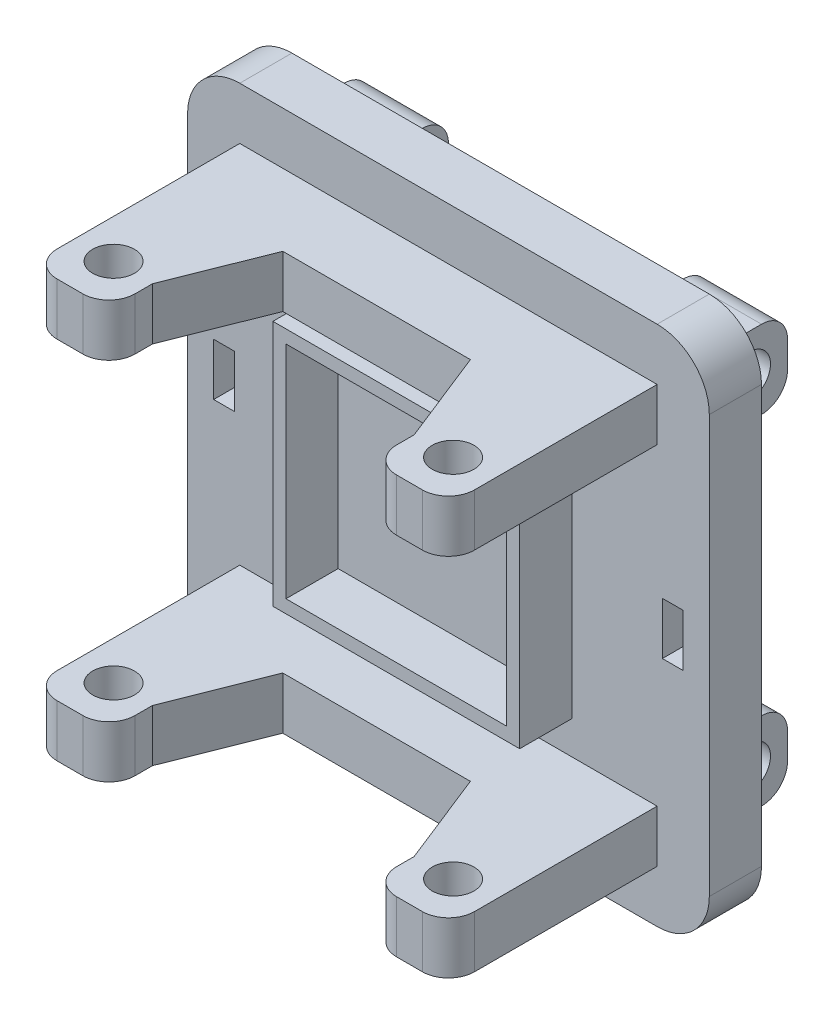
SolidWorks part; units mm, degrees
ref_plane "Piano frontale" through (0, 0, 0) normal (0, 0, 1) x (1, 0, 0)
ref_plane "Piano superiore" through (0, 0, 0) normal (0, 1, 0) x (1, 0, 0)
ref_plane "Piano destro" through (0, 0, 0) normal (1, 0, 0) x (0, 0, -1)
sketch "Schizzo1" plane through (0, 0, 0) normal (0, 0, 1) x (1, 0, 0)
  line L1 (-50, 50) -> (50, 50)
  line L2 (-50, 50) -> (-50, -50)
  line L3 (-50, -50) -> (50, -50)
  line L4 (50, 50) -> (50, -50)
  line L5 (-50, 50) -> (50, -50) construction
  line L6 (-50, -50) -> (50, 50) construction
  point P0 (0, 0)
  dimension "D1" = 100
  dimension "D2" = 100
extrude "Estrusione-Estrusione1" add sketch "Schizzo1" along normal blind 10
fillet "Raccordo1" radius 10 4 edges at (50, -50, 5) (-50, -50, 5) (50, 50, 5) (-50, 50, 5)
sketch "Schizzo5" plane through (0, 0, 0) normal (0, 0, -1) x (-1, 0, 0)
  line L0 (-50, 40) -> (50, 40) construction
  line L1 (50, 40) -> (-50, -40) construction
  line L2 (-50, -40) -> (-50, 40) construction
  line L3 (-50, -40) -> (50, -40) construction
  line L4 (50, -40) -> (-50, 40) construction
  line L5 (0, 57.1134) -> (0, 0) construction
  line L6 (0, 0) -> (66.1216, 0) construction
  arc A0 (-50, -40) -> (-40, -50) centre (-40, -40) ccw construction
ref_plane "Piano1" through (0, 0, 0) normal (0, 0, -1) x (-1, 0, 0)
sketch "Schizzo6" plane through (0, 0, 0) normal (0, 0, -1) x (-1, 0, 0)
  line L1 (-40, 40) -> (-25, 40)
  line L2 (-40, 40) -> (-40, 25)
  line L3 (-40, 25) -> (-25, 25)
  line L4 (-25, 40) -> (-25, 25)
  dimension "D1" = 15
  dimension "D2" = 15
extrude "Estrusione-Estrusione2" add sketch "Schizzo6" along normal blind 15
fillet "Raccordo2" radius 5 2 edges at (32.5, 25, -15) (32.5, 40, -15)
sketch "Schizzo7" plane through (40, 0, 0) normal (1, 0, 0) x (0, 0, -1)
  circle A0 centre (7.7265, 32.5421) radius 4
extrude "Taglio-Estrusione1" cut sketch "Schizzo7" against normal blind 15 contours A0
mirror "Specchia3" about plane through (0, 0, 0) normal (1, 0, 0) of "Estrusione-Estrusione2", "Taglio-Estrusione1"
fillet "Raccordo3" radius 5 2 edges at (-32.5, 25, -15) (-32.5, 40, -15)
mirror "Specchia6" about plane through (0, 0, 0) normal (0, 1, 0) of "Specchia3", "Raccordo3"
fillet "Raccordo4" radius 5 2 edges at (32.5, -40, -15) (32.5, -25, -15)
sketch "Schizzo8" plane through (0, 0, 10) normal (0, 0, 1) x (1, 0, 0)
  line L1 (-21.15, 21.15) -> (21.15, 21.15)
  line L2 (-21.15, 21.15) -> (-21.15, -21.15)
  line L3 (-21.15, -21.15) -> (21.15, -21.15)
  line L4 (21.15, 21.15) -> (21.15, -21.15)
  line L5 (-21.15, 21.15) -> (21.15, -21.15) construction
  line L6 (-21.15, -21.15) -> (21.15, 21.15) construction
  line L7 (-23.65, 23.65) -> (23.65, 23.65)
  line L8 (-23.65, 23.65) -> (-23.65, -23.65)
  line L9 (-23.65, -23.65) -> (23.65, -23.65)
  line L10 (23.65, 23.65) -> (23.65, -23.65)
  line L11 (-23.65, 23.65) -> (23.65, -23.65) construction
  line L12 (-23.65, -23.65) -> (23.65, 23.65) construction
  point P0 (0, 0)
  point P6 (0, 0)
  dimension "D1" = 42.3
  dimension "D2" = 42.3
  dimension "D3" = 47.3
  dimension "D4" = 47.3
extrude "Estrusione-Estrusione4" add sketch "Schizzo8" along normal blind 10
sketch "Schizzo10" plane through (0, 0, 10) normal (0, 0, 1) x (1, 0, 0)
  line L1 (40, -40) -> (-40, -40)
  line L2 (40, -40) -> (40, -30)
  line L3 (40, -30) -> (-40, -30)
  line L4 (-40, -40) -> (-40, -30)
  dimension "D1" = 10
extrude "Estrusione-Estrusione6" add sketch "Schizzo10" along normal blind 40 contours L2 L3 L4 L1
sketch "Schizzo11" plane through (0, -40, 0) normal (0, -1, 0) x (1, 0, 0)
  line L0 (-25.0784, 0) -> (-25.0784, 73.3) construction
  line L1 (50, 0) -> (-50, 0) construction
  line L2 (-25.0784, 73.3) -> (-40, 73.3) construction
  line L3 (-32.5392, 73.3) -> (-32.5392, 10) construction
  line L4 (-40, 10) -> (40, 10) construction
  line L5 (0, 0) -> (0, 59.9443) construction
  circle A0 centre (-32.5392, 41.65) radius 4
  circle A1 centre (32.5392, 41.65) radius 4
extrude "Taglio-Estrusione4" cut sketch "Schizzo11" against normal blind 30 contours A1
extrude "Taglio-Estrusione5" cut sketch "Schizzo11<4>" against normal blind 30
sketch "Schizzo11<4>" plane through (0, -40, 0) normal (0, -1, 0) x (1, 0, 0) same geometry as "Schizzo11"
fillet "Raccordo5" radius 5 1 edges at (-40, -35, 50)
fillet "Raccordo6" radius 5 1 edges at (40, -35, 50)
sketch "Schizzo14" plane through (0, -40, 0) normal (0, -1, 0) x (1, 0, 0)
  line L0 (-32.5392, 41.65) -> (-40, 41.65) construction
  line L1 (-40, 45) -> (-40, 10) construction
  line L2 (-32.5392, 41.65) -> (-25.0784, 41.65) construction
  line L3 (-25.0784, 41.65) -> (-25.0784, 50)
  line L4 (35, 50) -> (-35, 50) construction
  line L5 (-25.0784, 41.65) -> (-17.9796, 23.7762)
  line L6 (-17.9796, 23.7762) -> (17.9796, 23.7762)
  line L7 (0, 0) -> (0, 44.6599) construction
  line L8 (25.0784, 41.65) -> (25.0784, 50)
  line L9 (25.0784, 41.65) -> (17.9796, 23.7762)
  line L10 (-25.0784, 50) -> (25.0784, 50)
  point P17 (0, 23.7762)
  dimension "D1" = 7.4608
extrude "Taglio-Estrusione6" cut sketch "Schizzo14" against normal blind 30 contours L5 L6 L9 L8 L10 L3
fillet "Raccordo7" radius 5 1 edges at (-25.0784, -35, 50)
fillet "Raccordo8" radius 5 1 edges at (25.0784, -35, 50)
mirror "Specchia13" about plane through (0, 0, 0) normal (0, 1, 0) of "Estrusione-Estrusione6"
mirror "Specchia14" about plane through (0, 0, 0) normal (0, 1, 0) of "Estrusione-Estrusione6", "Taglio-Estrusione6"
fillet "Raccordo9" radius 5 4 edges at (-40, 35, 50) (-25.0784, 35, 50) (40, 35, 50) (25.0784, 35, 50)
sketch "Schizzo15" plane through (0, 40, 0) normal (0, 1, 0) x (1, 0, 0)
  line L0 (32.5392, -50) -> (32.5392, -33.3) construction
  line L1 (35, -50) -> (30.0784, -50) construction
  line L2 (0, 0) -> (0, -57.2659) construction
  circle A0 centre (32.5392, -41.65) radius 4
  circle A1 centre (-32.5392, -41.65) radius 4
  dimension "D1" = 8.35
extrude "Taglio-Estrusione7" cut sketch "Schizzo15" against normal blind 30 contours A0
extrude "Taglio-Estrusione8" cut sketch "Schizzo15<3>" against normal blind 30
sketch "Schizzo15<3>" plane through (0, 40, 0) normal (0, 1, 0) x (1, 0, 0) same geometry as "Schizzo15"
sketch "Schizzo16" plane through (0, 0, 0) normal (0, 0, -1) x (-1, 0, 0)
  line L0 (47.0711, 47.0711) -> (-47.0711, -47.0711) construction
  line L1 (0, 0) -> (43.631, 0) construction
  line L2 (47.0711, -47.0711) -> (-47.0711, 47.0711) construction
  line L4 (0, 47.0711) -> (0, -40) construction
  line L5 (-45, -5) -> (-41, -5)
  line L6 (-41, -5) -> (-41, 5)
  line L8 (-45, 5) -> (-41, 5)
  line L9 (-45, -5) -> (-45, 5)
  line L15 (0, 0) -> (-47.0711, 0) construction
  line L16 (50, 40) -> (50, -40) construction
  line L17 (45, -5) -> (41, -5)
  line L18 (45, -5) -> (45, 5)
  line L19 (45, 5) -> (41, 5)
  line L20 (41, -5) -> (41, 5)
  line L21 (45, -5) -> (41, 5) construction
  line L22 (45, 5) -> (41, -5) construction
  arc A0 (50, 40) -> (40, 50) centre (40, 40) ccw construction
  arc A1 (-50, -40) -> (-40, -50) centre (-40, -40) ccw construction
  arc A2 (40, -50) -> (50, -40) centre (40, -40) ccw construction
  arc A3 (-40, 50) -> (-50, 40) centre (-40, 40) ccw construction
  point P21 (0, -43)
  point P26 (43, 0)
  dimension "D4" = 4
  dimension "D5" = 10
  dimension "D6" = 9
extrude "Taglio-Estrusione11" cut sketch "Schizzo16" against normal blind 10
